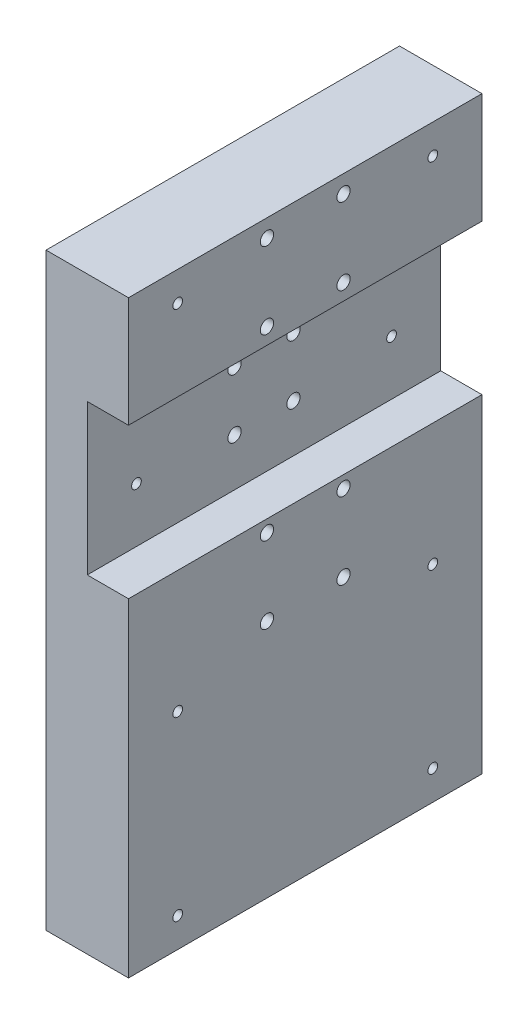
SolidWorks part; units mm, degrees
ref_plane "Front Plane" through (0, 0, 0) normal (0, 0, 1) x (1, 0, 0)
ref_plane "Top Plane" through (0, 0, 0) normal (0, 1, 0) x (1, 0, 0)
ref_plane "Right Plane" through (0, 0, 0) normal (1, 0, 0) x (0, 0, -1)
sketch "Sketch1" plane through (0, 0, 0) normal (0, 0, 1) x (1, 0, 0)
  line L0 (0, 0) -> (0, 200)
  line L1 (0, 200) -> (28, 200)
  line L2 (28, 200) -> (28, 162.5)
  line L3 (14, 162.5) -> (14, 111.5)
  line L4 (14, 162.5) -> (28, 162.5)
  line L5 (14, 111.5) -> (28, 111.5)
  line L6 (28, 111.5) -> (28, 0)
  line L7 (28, 0) -> (0, 0)
  line L8 (-49.525, 137) -> (95.9642, 137) construction
  point P12 (14, 137)
  dimension "D1" = 200
  dimension "D2" = 25.5
  dimension "D4" = 28
  dimension "D6" = 63
extrude "Boss-Extrude1" add sketch "Sketch1" along normal blind 120 contours L0 L1 L2 L4 L3 L5 L6 L7
sketch "Sketch2" plane through (0, 0, 0) normal (-1, 0, 0) x (0, 0, 1)
  line L0 (60, 200) -> (60, 0) construction
  line L1 (120, 200) -> (0, 200) construction
  line L2 (120, 0) -> (0, 0) construction
  point P6 (73, 194)
  point P7 (73, 168)
  point P8 (70, 147.7)
  point P9 (70, 127.7)
  point P10 (73, 107.4)
  point P11 (73, 81.4)
  point P12 (47, 81.4)
  point P13 (47, 107.4)
  point P14 (50, 127.7)
  point P15 (50, 147.7)
  point P16 (47, 168)
  point P17 (47, 194)
  dimension "D1" = 6
  dimension "D2" = 26
  dimension "D3" = 46.3
  dimension "D4" = 20
  dimension "D5" = 20.3
  dimension "D6" = 26
  dimension "D7" = 13
  dimension "D8" = 10
hole_wizard "CBORE for M4 SHCS4" positions "3DSketch2" profile "Sketch4" counterbore size "M4" standard "ANSI Metric" end condition through all
sketch3d "3DSketch2"
  point P0 (0, 194, 73)
  point P3 (0, 168, 73)
  point P6 (0, 147.7, 70)
  point P9 (0, 127.7, 70)
  point P12 (0, 107.4, 73)
  point P15 (0, 81.4, 73)
  point P18 (0, 81.4, 47)
  point P21 (0, 107.4, 47)
  point P24 (0, 127.7, 50)
  point P27 (0, 147.7, 50)
  point P30 (0, 168, 47)
  point P33 (0, 194, 47)
sketch "Sketch4" plane through (0, 194, 73) normal (0, 1, 0) x (0, 0, 1)
  line L0 (0, 0) -> (0, 28)
  line L1 (0, 28) -> (2.25, 28)
  line L3 (2.25, 28) -> (2.25, 4)
  line L4 (2.25, 4) -> (4, 4)
  line L5 (4, 4) -> (4, 0)
  line L7 (4, 0) -> (0, 0)
  line L11 (0, -6.35) -> (0, 107.95) construction
  dimension "Thru Hole Dia." = 4.5
  dimension "Thru Hole Depth" = 28
  dimension "C'Bore Dia." = 8
  dimension "C'Bore Depth" = 4
sketch "Sketch5" plane through (0, 0, 0) normal (-1, 0, 0) x (0, 0, 1)
  line L0 (16.7, 200) -> (16.7, 0) construction
  line L1 (120, 200) -> (0, 200) construction
  line L2 (120, 0) -> (0, 0) construction
  line L3 (60, 200) -> (60, 0) construction
  line L4 (60, 200) -> (60, 0) construction
  line L5 (103.3, 200) -> (103.3, 0) construction
  point P12 (16.7, 190)
  point P13 (103.3, 10)
  point P14 (16.7, 130)
  point P15 (16.7, 70)
  point P16 (16.7, 10)
  point P17 (103.3, 70)
  point P18 (103.3, 130)
  point P19 (103.3, 190)
  dimension "D1" = 43.3
  dimension "D2" = 10
  dimension "D3" = 4
hole_wizard "M4 Tapped Hole1" positions "3DSketch3" profile "Sketch6" tap size "M4" standard "ISO" end condition through all
sketch3d "3DSketch3"
  point P0 (0, 190, 16.7)
  point P3 (0, 130, 16.7)
  point P6 (0, 70, 16.7)
  point P9 (0, 10, 16.7)
  point P12 (0, 10, 103.3)
  point P15 (0, 70, 103.3)
  point P18 (0, 130, 103.3)
  point P21 (0, 190, 103.3)
sketch "Sketch6" plane through (0, 190, 16.7) normal (0, 1, 0) x (0, 0, 1)
  line L0 (0, 0) -> (0, 28)
  line L1 (0, 28) -> (1.65, 28)
  line L2 (1.65, 28) -> (1.65, 0)
  line L5 (1.65, 0) -> (0, 0)
  line L11 (0, -6.35) -> (0, 107.95) construction
  dimension "Thread Major Dia." = 3.3
  dimension "Thru Tap Drill Depth" = 28
ref_plane "Plane1" through (0, 0, 60) normal (0, 0, -1) x (-1, 0, 0)
sketch "Sketch7" plane through (0, 0, 0) normal (0, -1, 0) x (1, 0, 0)
  line L0 (14, 120) -> (14, 0) construction
  line L1 (28, 120) -> (0, 120) construction
  line L2 (28, 0) -> (0, 0) construction
  line L3 (28, 60) -> (0, 60) construction
  line L4 (28, 120) -> (28, 0) construction
  line L5 (0, 120) -> (0, 0) construction
  point P12 (14, 60)
  point P13 (14, 90)
  point P14 (14, 30)
  dimension "D1" = 30
hole_wizard "M5 Tapped Hole1" positions "3DSketch4" profile "Sketch8" tap size "M5" standard "ISO"
sketch3d "3DSketch4"
  point P0 (14, 0, 90)
  point P3 (14, 0, 60)
  point P6 (14, 0, 30)
sketch "Sketch8" plane through (14, 0, 90) normal (1, 0, 0) x (0, 0, -1)
  line L0 (0, 0) -> (0, 18.6618)
  line L1 (0, 18.6618) -> (2.1, 17.4)
  line L2 (2.1, 17.4) -> (2.1, 0)
  line L5 (2.1, 0) -> (0, 0)
  line L10 (0, 18.6618) -> (-2.1, 17.4) construction
  line L11 (0, -6.35) -> (0, 107.95) construction
  dimension "Tap Drill Dia." = 4.2
  dimension "Tap Drill Depth" = 17.4
  dimension "Drill Angle" = 118
